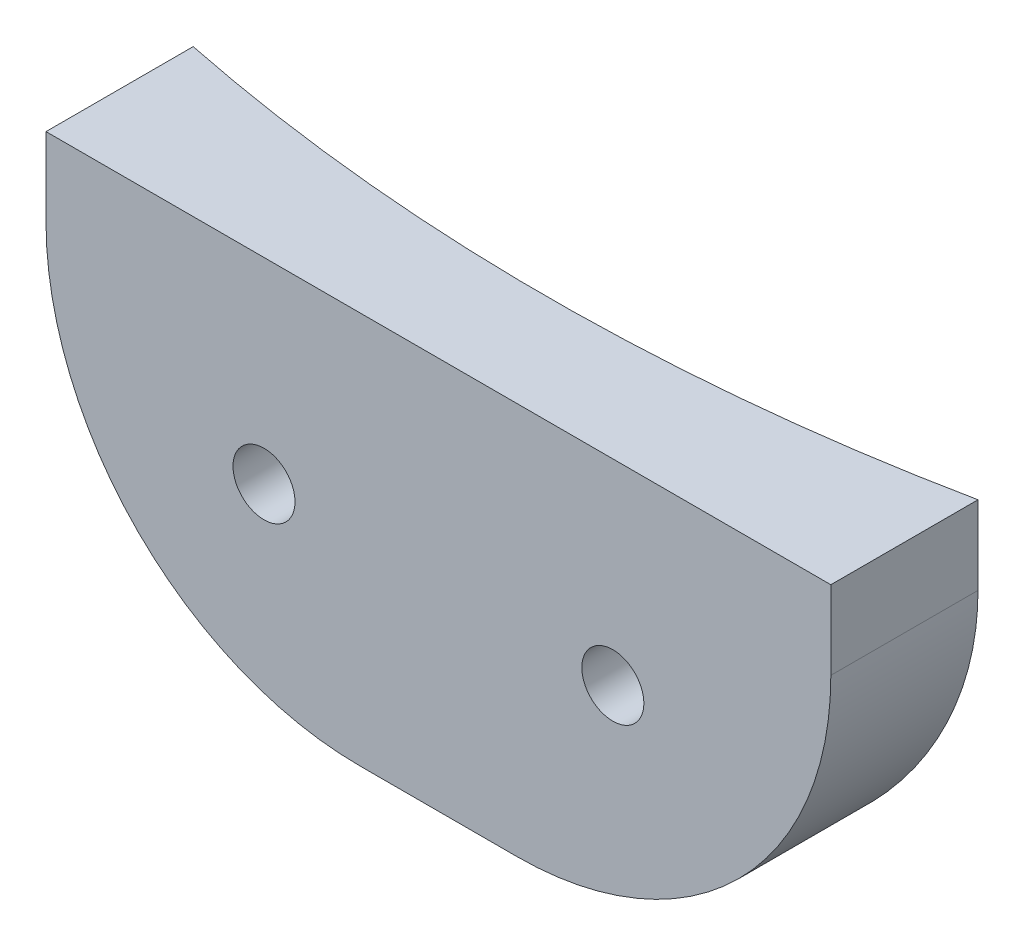
SolidWorks part; units mm, degrees
material "6061 Alloy"
ref_plane "Front Plane" through (0, 0, 0) normal (0, 0, 1) x (1, 0, 0)
ref_plane "Top Plane" through (0, 0, 0) normal (0, 1, 0) x (1, 0, 0)
ref_plane "Right Plane" through (0, 0, 0) normal (1, 0, 0) x (0, 0, -1)
sketch "Sketch1" plane through (0, 0, 0) normal (0, 1, 0) x (1, 0, 0)
  line L0 (-12.7, -62.217) -> (-12.7, -65.4543)
  line L1 (12.7, -62.217) -> (12.7, -65.4543)
  line L2 (-12.7, -66.9795) -> (12.7, -66.9795)
  line L3 (-12.7, -65.4543) -> (-12.7, -66.9795)
  line L4 (12.7, -65.4543) -> (12.7, -66.9795)
  circle A0 centre (0, 0) radius 63.5
  circle A1 centre (0, 0) radius 66.675
  dimension "D1" = 127
  dimension "D3" = 12.7
  dimension "D4" = 12.7
  dimension "D5" = 4.7625
  dimension "D2" = 3.175
extrude "Boss-Extrude1" add sketch "Sketch1" along normal blind 12.7 contours L0 A1 L1 A0 | A1 L3 L2 | A1 L2 L4 region at (0, 0, 64.6697) region at (0, 0, 66.9295)
sketch "Sketch2" plane through (0, 0, 0) normal (0, 0, 1) x (1, 0, 0)
  line L0 (0, 12.7) -> (0, 0) construction
  line L5 (-12.7, 0) -> (12.7, 0)
  line L6 (12.7, 0) -> (12.7, 12.7)
  line L7 (12.7, 12.7) -> (-12.7, 12.7)
  line L12 (-12.7, 12.7) -> (-12.7, 0)
  line L13 (-12.7, 0) -> (12.7, 0)
  line L14 (12.7, 0) -> (12.7, 12.7)
  line L15 (12.7, 12.7) -> (-12.7, 12.7)
  line L16 (-12.7, 12.7) -> (-12.7, 0)
  circle A0 centre (-5.6444, 6.35) radius 1.0033
  dimension "D6" = 2.0066
  dimension "D5" = 5.6444
  dimension "D2" = 6.35
extrude "Cut-Extrude1" cut sketch "Sketch2" along normal up to surface (66.9795 mm away) contours A0 up to face at (0, 6.35, 66.9795)
mirror "Mirror1" about plane through (0, 0, 0) normal (1, 0, 0) of "Cut-Extrude1"
sketch "Sketch3" plane through (0, 0, 0) normal (0, 0, 1) x (1, 0, 0)
  line L0 (-12.7, 12.7) -> (-12.7, 0)
  line L6 (-12.7, 0) -> (0, 0)
  line L7 (12.7, 12.7) -> (12.7, 0)
  line L8 (-2.54, 0) -> (2.54, 0)
  line L9 (12.7, 10.16) -> (12.7, 12.7)
  line L10 (12.7, 12.7) -> (-12.7, 12.7)
  line L11 (-12.7, 12.7) -> (-12.7, 10.16)
  line L12 (12.7, 0) -> (2.54, 0)
  arc A0 (2.54, 0) -> (12.7, 10.16) centre (2.54, 10.16) ccw
  arc A1 (-2.54, 0) -> (-12.7, 10.16) centre (-2.54, 10.16) cw
  dimension "D2" = 10.16
  dimension "D6" = 2.54
  dimension "D1" = 12.7
  dimension "D3" = 12.7
  dimension "D4" = 2.54
  dimension "D5" = 2.54
  dimension "D7" = 2.54
  dimension "D8" = 2.54
  dimension "D9" = 10.16
extrude "Cut-Extrude2" cut sketch "Sketch3" along normal up to surface (66.9795 mm away) contours L6 A1 L0 | A0 L12 L7 region at (-10.4306, 2.2694, 0) region at (10.4306, 2.2694, 0) up to face at (4.6411, 6.35, 66.9795)
equation "\"Middle Coupler Inner Daimeter\"= 4.5in"
equation "\"Middle Coupler  Wall Thickness\" = 0.25in"
equation "\"Middle Coupler Bottom Thickness\"= 0.2in"
equation "\"Bearing Rail Offset\"= 0.45in"
equation "\"3-56 UNF Tap\"= 0.089in"
equation "\"3-56 UNF Clearance\"= 0.104in"
equation "\"Ball Bearing Distance\"= 0.03in"
equation "\"TCA Outer Diameter\" = 6.625in"
equation "\"D1@Sketch1\"=\"Middle Coupler Inner Daimeter\"+0.5"
equation "\"D2@Sketch1\"=1/8"
equation "\"D3@Sketch1\"=0.5"
equation "\"D4@Sketch1\"=\"D3@Sketch1\""
equation "\"D6@Sketch2\"=\"3-48 Tap\""
equation "\"Interstage Aeroframe Wall Thickness\" = 0.072in"
equation "\"Compression Spring OD\"= 0.42in"
equation "\"10-24 Tap\"= 0.157in"
equation "\"10-24 Clearance\"= 0.196in"
equation "\"Lower Stage Fuselage Wall Thickness\" = 0.25in"
equation "\"6-32 Tap\" = 0.107in"
equation "\"1/4-20 Tap\" = 0.201in"
equation "\"3-48 Tap\"= 0.079in"
equation "\"3-48 Clearance\" = 0.104in"
equation "\"6-32 Clearance\" = 0.144"
equation "\"12-24 Tap\" = 0.177in"
equation "\"D5@Sketch1\"=3/16"
